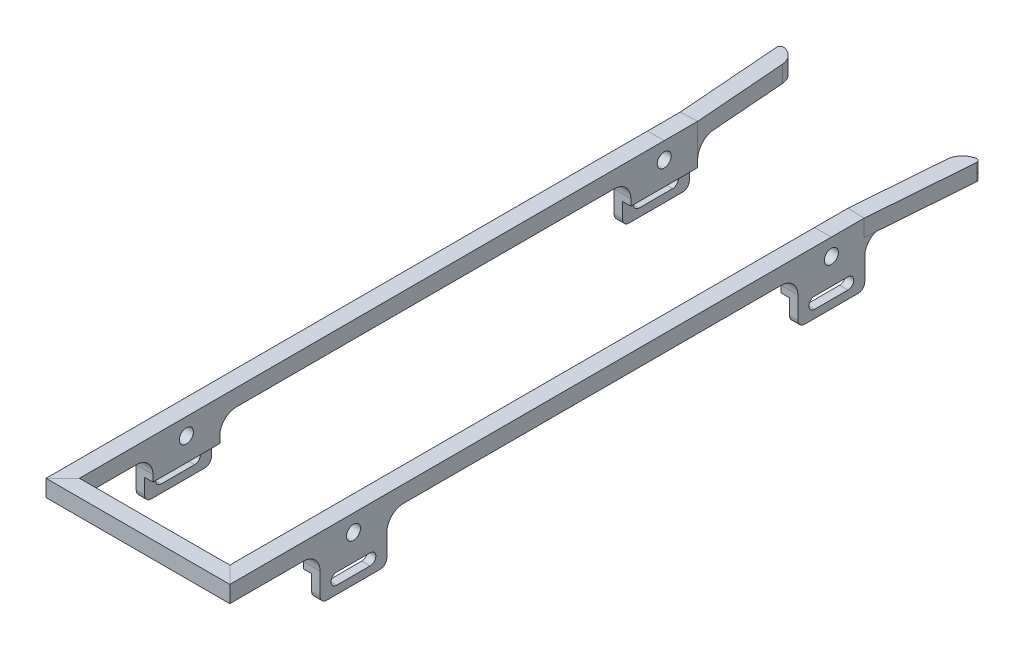
SolidWorks part; units mm, degrees
ref_plane "Front Plane" through (0, 0, 0) normal (0, 0, 1) x (1, 0, 0)
ref_plane "Top Plane" through (0, 0, 0) normal (0, 1, 0) x (1, 0, 0)
ref_plane "Right Plane" through (0, 0, 0) normal (1, 0, 0) x (0, 0, -1)
sketch "rail_path" plane through (0, 0, 0) normal (0, 1, 0) x (1, 0, 0)
  line L0 (28.575, 111.125) -> (28.575, 123.825)
  line L1 (-28.575, -111.125) -> (28.575, -111.125)
  line L2 (-28.575, -111.125) -> (-28.575, 111.125)
  line L3 (-28.575, 111.125) -> (28.575, 111.125) construction
  line L4 (28.575, -111.125) -> (28.575, 111.125)
  line L5 (-28.575, -111.125) -> (28.575, 111.125) construction
  line L6 (-28.575, 111.125) -> (28.575, -111.125) construction
  line L7 (-28.575, 111.125) -> (-28.575, 123.825)
  line L8 (28.575, 123.825) -> (31.75, 165.1)
  line L9 (-28.575, 123.825) -> (-31.75, 165.1)
  point P0 (0, 0)
  dimension "D1" = 222.25
  dimension "D2" = 57.15
  dimension "D3" = 12.7
  dimension "D4" = 12.7
  dimension "D5" = 41.275
  dimension "D6" = 3.175
  dimension "D7" = 3.175
sketch "rail_profile" plane through (0, 0, 0) normal (0, 0, 1) x (1, 0, 0)
  line L0 (-28.575, 0) -> (28.575, 0) construction
  line L1 (28.575, 0) -> (34.925, 0)
  line L2 (28.575, 0) -> (28.575, 6.35)
  line L3 (28.575, 6.35) -> (34.925, 6.35)
  line L4 (34.925, 0) -> (34.925, 6.35)
  line L5 (-28.575, 0) -> (28.575, 0) construction
  dimension "D1" = 6.35
  dimension "D2" = 6.35
sweep "Sweep1" add profiles "rail_profile" path "rail_path"
sketch "clip_profile" plane through (0, 0, 0) normal (0, 0, 1) x (1, 0, 0)
  line L4 (28.575, 0) -> (-28.575, 0)
  line L12 (-28.575, 6.35) -> (28.575, 6.35)
  line L34 (34.925, -17.272) -> (31.75, -17.272)
  line L38 (28.575, -8.89) -> (31.75, -8.89)
  line L39 (31.75, -17.272) -> (31.75, -8.89)
  line L47 (31.75, 6.35) -> (38.0813, 6.35)
  line L48 (34.925, -17.272) -> (34.925, -8.89)
  line L49 (38.0813, 6.35) -> (38.0813, 0)
  line L50 (28.575, -8.89) -> (34.925, -8.89)
  line L51 (28.575, -8.89) -> (28.575, 0)
  line L52 (28.575, 0) -> (34.925, 0)
  line L53 (34.925, -8.89) -> (34.925, 0)
  line L54 (31.75, 6.35) -> (38.0813, 6.35)
  line L55 (38.0813, 6.35) -> (38.0813, 0)
  line L56 (38.0813, 0) -> (31.75, 0)
  line L57 (31.75, 0) -> (28.575, 0)
  line L58 (38.0813, 0) -> (31.75, 0)
  line L59 (-28.575, 0) -> (-31.75, 0)
  line L60 (-31.75, 0) -> (-38.0813, 0)
  line L61 (-38.0813, 0) -> (-38.0813, 6.35)
  line L62 (-38.0813, 6.35) -> (-31.75, 6.35)
  line L63 (-31.75, 6.35) -> (-28.575, 6.35)
  line L64 (31.75, 0) -> (28.575, 0)
  line L65 (28.575, 6.35) -> (31.75, 6.35)
  line L66 (-28.575, 0) -> (-31.75, 0)
  line L67 (-31.75, 0) -> (-38.0813, 0)
  line L68 (-38.0813, 0) -> (-38.0813, 6.35)
  line L69 (-38.0813, 6.35) -> (-31.75, 6.35)
  line L70 (-31.75, 6.35) -> (-28.575, 6.35)
  line L71 (28.575, 6.35) -> (31.75, 6.35)
  dimension "D1" = 8.89
  dimension "D2" = 3.175
  dimension "D4" = 8.382
ref_plane "BackClipPlane" through (0, 0, 70.485) normal (0, 0, -1) x (-1, 0, 0)
ref_plane "FrontClipPlane" through (0, 0, -111.125) normal (0, 0, -1) x (-1, 0, 0)
sketch "BackClipProfile" plane through (0, 0, 70.485) normal (0, 0, -1) x (-1, 0, 0)
  line L24 (-34.925, -8.89) -> (-34.925, 0) construction
  line L25 (-34.925, -17.272) -> (-34.925, -8.89) construction
  line L26 (-34.925, -17.272) -> (-31.75, -17.272) construction
  line L27 (-31.75, -17.272) -> (-31.75, -8.89) construction
  line L28 (-28.575, -8.89) -> (-31.75, -8.89) construction
  line L29 (-28.575, -8.89) -> (-28.575, 0) construction
  line L30 (-34.925, -8.89) -> (-34.925, 0)
  line L31 (-34.925, -17.272) -> (-34.925, -8.89)
  line L32 (-34.925, -17.272) -> (-31.75, -17.272)
  line L33 (-31.75, -17.272) -> (-31.75, -8.89)
  line L34 (-28.575, -8.89) -> (-31.75, -8.89)
  line L35 (-28.575, -8.89) -> (-28.575, 0)
  line L36 (-28.575, 0) -> (-34.925, 0)
sketch "FrontClipProfile" plane through (0, 0, -111.125) normal (0, 0, -1) x (-1, 0, 0)
  line L24 (-31.75, -17.272) -> (-31.75, -8.89) construction
  line L25 (-34.925, -17.272) -> (-31.75, -17.272) construction
  line L26 (-34.925, -17.272) -> (-34.925, -8.89) construction
  line L27 (-34.925, -8.89) -> (-34.925, 0) construction
  line L28 (-28.575, -8.89) -> (-31.75, -8.89) construction
  line L29 (-28.575, -8.89) -> (-28.575, 0) construction
  line L30 (-31.75, -17.272) -> (-31.75, -8.89)
  line L31 (-34.925, -17.272) -> (-31.75, -17.272)
  line L32 (-34.925, -17.272) -> (-34.925, -8.89)
  line L33 (-34.925, -8.89) -> (-34.925, 0)
  line L34 (-28.575, -8.89) -> (-31.75, -8.89)
  line L35 (-28.575, -8.89) -> (-28.575, 0)
  line L36 (-28.575, 0) -> (-34.925, 0)
extrude "BackClip" add sketch "BackClipProfile" along normal mid plane 25.4
mirror "BackClipMirror" about plane through (0, 0, 0) normal (1, 0, 0) of "BackClip"
extrude "FrontClip" add sketch "FrontClipProfile" along normal mid plane 25.4
mirror "FrontClipMirror" about plane through (0, 0, 0) normal (1, 0, 0) of "FrontClip"
sketch "Sketch8" plane through (28.575, 0, 0) normal (-1, 0, 0) x (0, 0, 1)
  line L0 (70.485, 3.4925) -> (70.485, -3.4925) construction
  line L9 (111.125, 6.35) -> (-111.125, 6.35) construction
  line L17 (111.125, 6.35) -> (-111.125, 6.35) construction
  circle A2 centre (70.485, 0) radius 2.667
  dimension "D2" = 5.334
extrude "Cut-Extrude1" cut sketch "Sketch8" against normal through all both and the other way through all
ref_plane "Plane1" through (0, 0, -20.32) normal (0, 0, -1) x (-1, 0, 0)
sketch "Sketch10" plane through (31.75, 0, 0) normal (-1, 0, 0) x (0, 0, 1)
  line L0 (64.135, -12.065) -> (76.835, -12.065) construction
  line L1 (64.135, -9.906) -> (76.835, -9.906)
  line L2 (64.135, -14.224) -> (76.835, -14.224)
  line L3 (57.785, -8.89) -> (83.185, -8.89) construction
  line L4 (70.485, 3.4925) -> (70.485, -3.4925) construction
  arc A0 (64.135, -9.906) -> (64.135, -14.224) centre (64.135, -12.065) ccw
  arc A1 (76.835, -14.224) -> (76.835, -9.906) centre (76.835, -12.065) ccw
  point P2 (70.485, -12.065)
  dimension "D2" = 2.159
  dimension "D1" = 3.175
  dimension "D3" = 12.7
fillet "Fillet1" radius 2.54 8 edges at (-33.3375, -17.272, -123.825) (-33.3375, -17.272, -98.425) (-33.3375, -17.272, 57.785) (-33.3375, -17.272, 83.185) (33.3375, -17.272, 57.785) (33.3375, -17.272, 83.185) (33.3375, -17.272, -98.425) (33.3375, -17.272, -123.825)
mirror "Mirror2" about plane through (0, 0, -20.32) normal (0, 0, -1) of "Cut-Extrude1"
extrude "Cut-Extrude3" cut sketch "Sketch10" against normal through all both and the other way through all
mirror "Mirror3" about plane through (0, 0, -20.32) normal (0, 0, -1) of "Cut-Extrude3"
fillet "Fillet3" radius 6.35 2 edges at (31.75, 3.175, -165.1) (-31.75, 3.175, -165.1)
fillet "Fillet5" radius 1.27 2 edges at (38.0813, 3.175, -164.613) (-38.0813, 3.175, -164.613)
fillet "Fillet10" radius 6.35 8 edges at (-31.75, 0, 57.785) (-31.75, 0, 83.185) (31.75, 0, 83.185) (31.75, 0, 57.785) (31.75, 0, -98.425) (-31.75, 0, -98.425) (31.75, 0, -123.825) (-31.75, 0, -123.825)
equation "\"rail_horizontal_clearance\"= 0.25 / 2"
